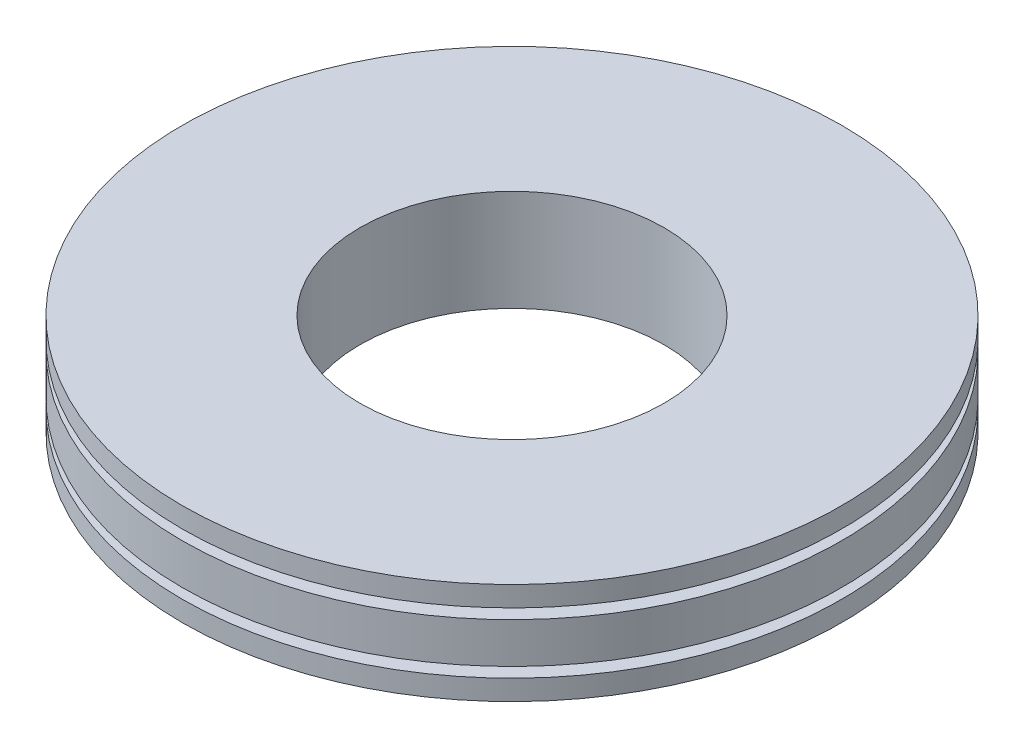
SolidWorks part; units mm, degrees
ref_plane "前视基准面" through (0, 0, 0) normal (0, 0, 1) x (1, 0, 0)
ref_plane "上视基准面" through (0, 0, 0) normal (0, 1, 0) x (1, 0, 0)
ref_plane "右视基准面" through (0, 0, 0) normal (1, 0, 0) x (0, 0, -1)
sketch "草图1" plane through (0, 0, 0) normal (0, 1, 0) x (1, 0, 0)
  circle A0 centre (0, 0) radius 13
extrude "凸台-拉伸1" add sketch "草图1" along normal blind 4
sketch "草图2" plane through (0, 0, 0) normal (0, -1, 0) x (1, 0, 0)
  circle A0 centre (0, 0) radius 6
extrude "切除-拉伸1" cut sketch "草图2" against normal blind 4
sketch "草图3" plane through (0, 0, 0) normal (0, -1, 0) x (1, 0, 0)
  circle A0 centre (0, 0) radius 13
  circle A1 centre (0, 0) radius 12
extrude "切除-拉伸2" cut sketch "草图3" against normal blind 0.4 from offset 0.8 offset against normal yes
extrude "切除-拉伸3" cut sketch "草图3<3>" along normal blind 0.4 from offset 3.2 offset against normal yes
sketch "草图3<3>" plane through (0, 0, 0) normal (0, -1, 0) x (1, 0, 0) same geometry as "草图3"
